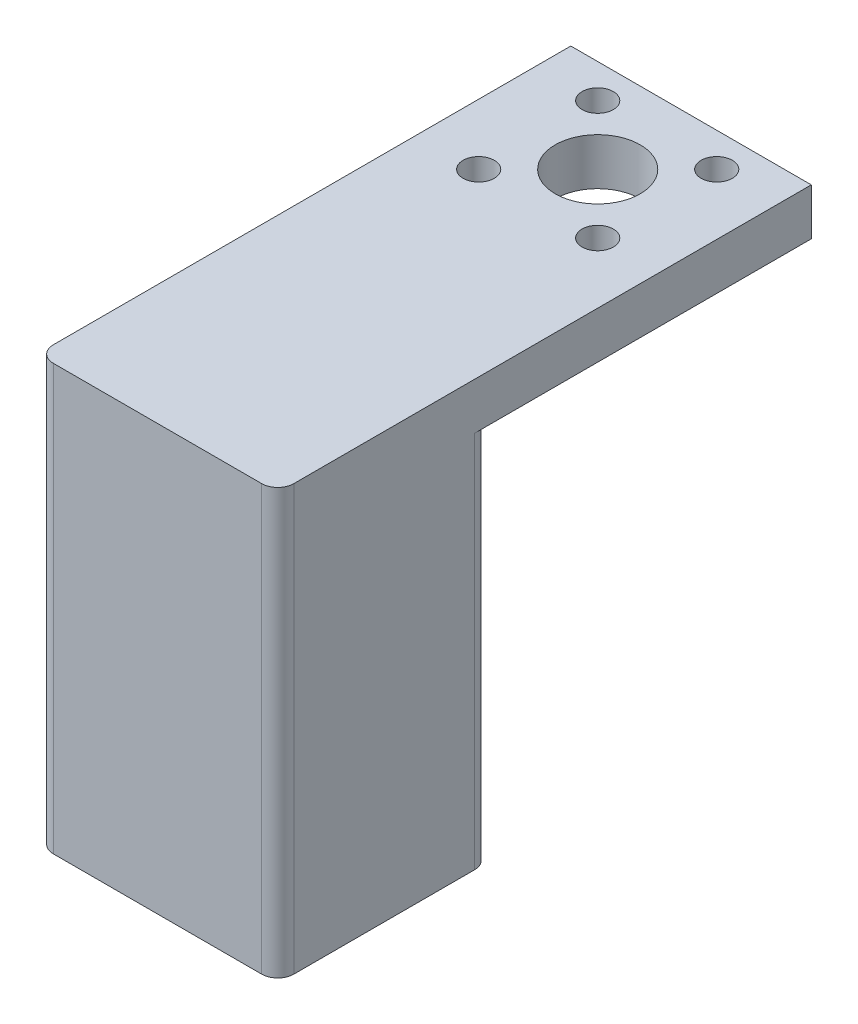
SolidWorks part; units mm, degrees
ref_plane "Alzado" through (0, 0, 0) normal (0, 0, 1) x (1, 0, 0)
ref_plane "Planta" through (0, 0, 0) normal (0, 1, 0) x (1, 0, 0)
ref_plane "Vista lateral" through (0, 0, 0) normal (1, 0, 0) x (0, 0, -1)
sketch "Croquis1" plane through (0, 0, 0) normal (0, 1, 0) x (1, 0, 0)
  line L1 (-15, 13.2786) -> (15, 13.2786)
  line L2 (-15, 13.2786) -> (-15, -13.2786)
  line L3 (-15, -13.2786) -> (15, -13.2786)
  line L4 (15, 13.2786) -> (15, -13.2786)
  line L5 (-15, 13.2786) -> (15, -13.2786) construction
  line L6 (-15, -13.2786) -> (15, 13.2786) construction
  line L7 (-12, 10.6229) -> (12, 10.6229)
  line L8 (-12, 10.6229) -> (-12, -10.6229)
  line L9 (-12, -10.6229) -> (12, -10.6229)
  line L10 (12, 10.6229) -> (12, -10.6229)
  line L11 (-12, 10.6229) -> (12, -10.6229) construction
  line L12 (-12, -10.6229) -> (12, 10.6229) construction
  point P0 (0, 0)
  point P6 (0, 0)
  dimension "D1" = 30
  dimension "D2" = 3
extrude "Saliente-Extruir1" add sketch "Croquis1" along normal blind 50
sketch "Croquis2" plane through (0, 50, 0) normal (0, 1, 0) x (1, 0, 0)
  line L1 (-15, 13.2786) -> (15, 13.2786)
  line L2 (-15, 13.2786) -> (-15, -13.2786)
  line L3 (-15, -13.2786) -> (15, -13.2786)
  line L4 (15, 13.2786) -> (15, -13.2786)
extrude "Saliente-Extruir2" add sketch "Croquis2" along normal blind 3
sketch "Croquis6" plane through (0, 0, -13.2786) normal (0, 0, -1) x (-1, 0, 0)
  line L0 (-15, 53) -> (-15, 0) construction
  line L1 (15, 53) -> (-15, 53)
  line L2 (15, 53) -> (15, 47.1624)
  line L3 (15, 47.1624) -> (-15, 47.1624)
  line L4 (-15, 53) -> (-15, 47.1624)
extrude "Saliente-Extruir4" add sketch "Croquis6" along normal blind 40
sketch "Croquis7" plane through (0, 53, 0) normal (0, 1, 0) x (1, 0, 0)
  line L0 (0, 41.6346) -> (10.5, 41.6346) construction
  line L1 (0, 41.6346) -> (7.4246, 49.0592) construction
  line L2 (0, 53.2786) -> (0, 22.7161) construction
  line L3 (-15, 53.2786) -> (15, 53.2786) construction
  circle A0 centre (0, 41.6346) radius 5.3
  circle A1 centre (0, 41.6346) radius 10.5 construction
  circle A2 centre (7.4246, 49.0592) radius 1.95
  circle A3 centre (7.4246, 34.21) radius 1.95
  circle A4 centre (-7.4246, 34.21) radius 1.95
  circle A5 centre (-7.4246, 49.0592) radius 1.95
  point P15 (0, 41.6346)
  dimension "D1" = 10.6
  dimension "D2" = 21
  dimension "D3" = 3.9
  dimension "D4" = 45
  dimension "D5" = 4
extrude "Cortar-Extruir2" cut sketch "Croquis7" against normal blind 40
fillet "Redondeo1" radius 2 8 edges at (-15, 26.5, 13.2786) (15, 26.5, 13.2786) (-12, 25, 10.6229) (-12, 25, -10.6229) (12, 25, 10.6229) (12, 25, -10.6229)
